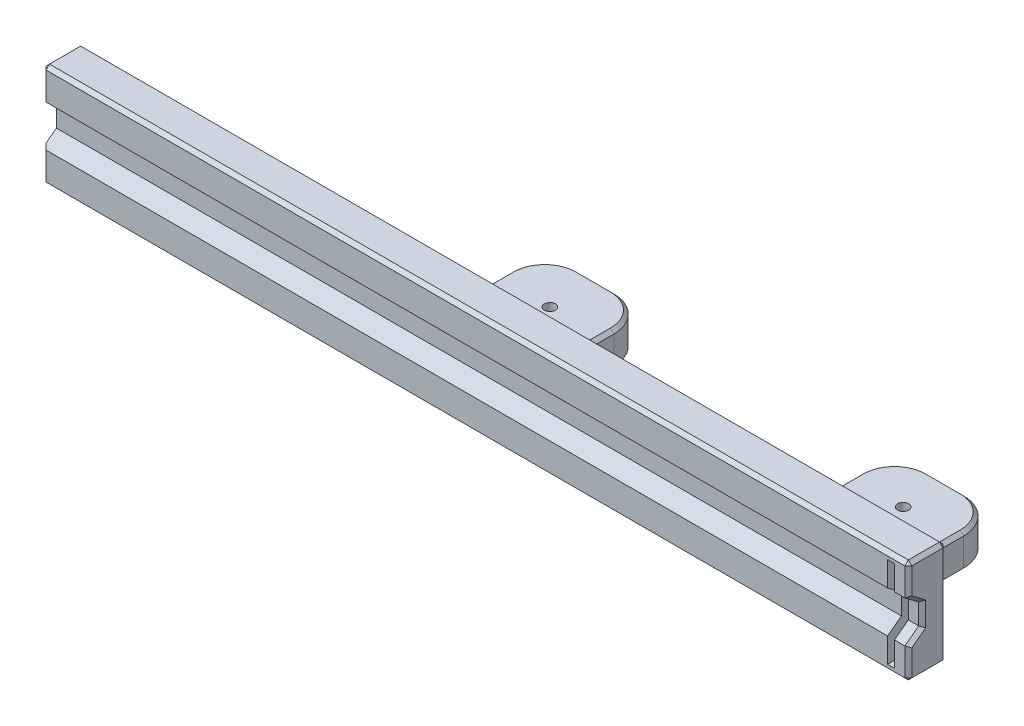
SolidWorks part; units mm, degrees
ref_plane "前基準面" through (0, 0, 0) normal (0, 0, 1) x (1, 0, 0)
ref_plane "上基準面" through (0, 0, 0) normal (0, 1, 0) x (1, 0, 0)
ref_plane "右基準面" through (0, 0, 0) normal (1, 0, 0) x (0, 0, -1)
sketch "草圖1" plane through (0, 0, 0) normal (0, 0, 1) x (1, 0, 0)
  line L0 (0, 0) -> (250, 0)
  line L1 (250, 0) -> (250, 30)
  line L2 (250, 30) -> (0, 30)
  line L3 (0, 30) -> (0, 0)
  dimension "D1" = 30
  dimension "D2" = 250
extrude "填料-伸長1" add sketch "草圖1" along normal blind 11
sketch "草圖4" plane through (0, 0, 0) normal (0, 0, -1) x (-1, 0, 0)
  line L0 (-250, 15) -> (0, 15)
  line L1 (-250, 0) -> (-250, 30) construction
  line L2 (0, 30) -> (0, 0) construction
  line L3 (-124, 30) -> (-124, 0)
  line L6 (-139, 15) -> (-125, 15)
  line L7 (-125, 15) -> (-109, 15)
  line L8 (-139, 15) -> (-139, 20)
  line L9 (-139, 20) -> (-109, 20)
  line L10 (-109, 20) -> (-109, 15)
  line L11 (-139, 15) -> (-139, 10)
  line L12 (-139, 10) -> (-124, 10)
  line L13 (-124, 10) -> (-109, 10)
  line L14 (-109, 10) -> (-109, 15)
  line L16 (-164.6389, 10) -> (-194.6389, 10)
  line L17 (-164.6389, 10) -> (-164.6389, 20)
  line L18 (-164.6389, 20) -> (-194.6389, 20)
  line L19 (-194.6389, 10) -> (-194.6389, 20)
  line L20 (-164.6389, 10) -> (-194.6389, 20) construction
  line L21 (-164.6389, 20) -> (-194.6389, 10) construction
  point P17 (-179.6389, 15)
  dimension "D1" = 15
  dimension "D2" = 15
  dimension "D3" = 5
  dimension "D4" = 5
  dimension "D5" = 10
  dimension "D6" = 30
  dimension "D7" = 126
extrude "填料-伸長2" add sketch "草圖4" along normal blind 25 contours L11 L12 L3 L0 | L9 L8 L0 L3 | L10 L9 L3 L0 | L13 L14 L0 L3 region at (131.5, 17.5, 0) region at (131.5, 12.5, 0) region at (116.5, 17.5, 0) region at (116.5, 12.5, 0)
sketch "草圖5" plane through (250, 0, 0) normal (1, 0, 0) x (0, 0, -1)
  line L0 (-11, 30) -> (-11, 21)
  line L1 (-11, 0) -> (-11, 30) construction
  line L2 (-7, 15) -> (-7, 12)
  line L3 (-7, 15) -> (-7, 18)
  line L4 (-7, 18) -> (-11, 21)
  line L5 (-11, 9) -> (-11, 0)
  line L6 (-11, 15) -> (0, 15)
  line L7 (0, 30) -> (0, 0) construction
  line L8 (-7, 12) -> (-11, 9)
  line L9 (-11, 9) -> (-11, 21)
  line M6 (-11, 30) -> (-11, 0)
  dimension "D1" = 12
  dimension "D2" = 30
  dimension "D3" = 6
  dimension "D4" = 3
  dimension "D5" = 3
  dimension "D6" = 4
extrude "除料-伸長2" cut sketch "草圖5" against normal through all contours L6 L3 L4 M6 | L8 L2 L6 M6 region at (250, 17.3333, 9.2222) region at (250, 12.6667, 9.2222)
sketch "草圖9" plane through (0, 0, 0) normal (0, 0, -1) x (-1, 0, 0)
  line L1 (-194.6389, 20) -> (-164.6389, 20)
  line L2 (-194.6389, 20) -> (-194.6389, 10)
  line L3 (-194.6389, 10) -> (-164.6389, 10)
  line L4 (-164.6389, 20) -> (-164.6389, 10)
  line L5 (-194.6389, 20) -> (-164.6389, 10) construction
  line L6 (-194.6389, 10) -> (-164.6389, 20) construction
  point P0 (-179.6389, 15)
sketch "草圖11" plane through (0, 0, 0) normal (0, 0, -1) x (-1, 0, 0)
  line L0 (-125, 15) -> (-225, 15)
  line L1 (-250, 15) -> (0, 15) construction
  line L3 (-240, 10) -> (-210, 10)
  line L4 (-240, 10) -> (-240, 20)
  line L5 (-240, 20) -> (-210, 20)
  line L6 (-210, 10) -> (-210, 20)
  line L7 (-240, 10) -> (-210, 20) construction
  line L8 (-240, 20) -> (-210, 10) construction
  dimension "D1" = 100
  dimension "D2" = 10
  dimension "D3" = 30
extrude "填料-伸長4" add sketch "草圖11" along normal blind 25 contours L3 L6 L5 L4 region at (239.6838, 15, 0)
sketch "草圖12" plane through (0, 20, 0) normal (0, 1, 0) x (1, 0, 0)
  line L0 (240, 12.5) -> (210, 12.5)
  line L1 (240, 25) -> (240, 0) construction
  line L2 (210, 25) -> (210, 0) construction
  line L3 (0, 0) -> (250, 0) construction
  circle A0 centre (225, 12.5) radius 1.6
  dimension "D1" = 3.2
  dimension "D2" = 12.5
extrude "除料-伸長5" cut sketch "草圖12" against normal through all contours A0
fillet "圓角1" radius 10 4 edges at (109, 15, -25) (139, 15, -25) (210, 15, -25) (240, 15, -25)
sketch "草圖13" plane through (0, 0, 11) normal (0, 0, 1) x (1, 0, 0)
  line L1 (244, 28.1) -> (246, 28.1)
  line L2 (244, 28.1) -> (244, 1.9)
  line L3 (244, 1.9) -> (246, 1.9)
  line L4 (246, 28.1) -> (246, 1.9)
  line L5 (250, 15) -> (0, 15) construction
  line L6 (250, 0) -> (250, 30) construction
  dimension "D1" = 2
  dimension "D2" = 26.2
  dimension "D3" = 13.1
  dimension "D4" = 4
extrude "除料-伸長6" cut sketch "草圖13" against normal through all
chamfer "導角1" distance 1 angle 45 45 edges at (250, 15, 0) (250, 30, 5.5) (250, 0, 5.5) (125, 30, 11) (125, 0, 11) (0, 30, 5.5) (125, 30, 0) (125, 0, 0) (0, 15, 0) (0, 0, 5.5) (225, 10, -25) (225, 20, -25) (212.9289, 20, -22.0711) (212.9289, 10, -22.0711) (237.0711, 10, -22.0711) (237.0711, 20, -22.0711) (225, 20, 0) (210, 20, -7.5) (210, 15, 0) (210, 10, -7.5) (225, 10, 0) (240, 10, -7.5) (240, 15, 0) (240, 20, -7.5) (124, 20, -25) (124, 10, -25) (111.9289, 20, -22.0711) (111.9289, 10, -22.0711) (136.0711, 20, -22.0711) (136.0711, 10, -22.0711) (109, 20, -7.5) (124, 10, 0) (109, 10, -7.5) (109, 15, 0) (124, 20, 0) (139, 20, -7.5) (139, 15, 0) (139, 10, -7.5) (250, 4.5, 11) (250, 10.5, 9) (250, 15, 7) (250, 19.5, 9) (250, 25.5, 11) (0, 25.5, 11) (0, 4.5, 11)
sketch "草圖15" plane through (0, 10, 0) normal (0, -1, 0) x (1, 0, 0)
  line L0 (1, 1) -> (249, 1) construction
  line L1 (139, -1) -> (139, -15) construction
  circle A0 centre (124, -11.5) radius 1.6
  point P6 (134.1657, -10.7605)
  dimension "D1" = 12.5
  dimension "D3" = 3.2
  dimension "D2" = 15
extrude "除料-伸長7" cut sketch "草圖15" against normal through all both and the other way through all contours A0
